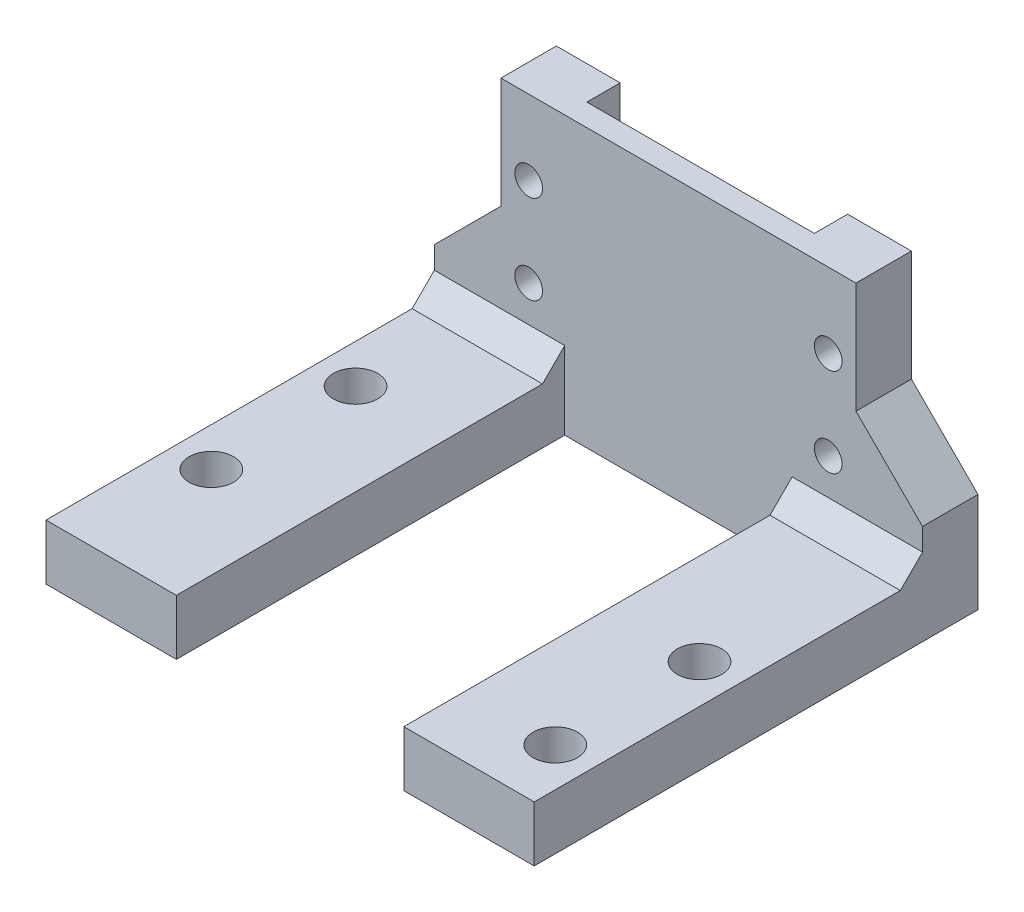
SolidWorks part; units mm, degrees
ref_plane "Płaszczyzna przednia" through (0, 0, 0) normal (0, 0, 1) x (1, 0, 0)
ref_plane "Płaszczyzna górna" through (0, 0, 0) normal (0, 1, 0) x (1, 0, 0)
ref_plane "Płaszczyzna prawa" through (0, 0, 0) normal (1, 0, 0) x (0, 0, -1)
sketch "Szkic1" plane through (0, 0, 0) normal (0, 0, 1) x (1, 0, 0)
  line L1 (16, -12.5) -> (-16, -12.5)
  line L2 (16, -12.5) -> (16, 12.5)
  line L3 (16, 12.5) -> (-16, 12.5)
  line L4 (-16, -12.5) -> (-16, 12.5)
  line L5 (16, -12.5) -> (-16, 12.5) construction
  line L6 (16, 12.5) -> (-16, -12.5) construction
  point P0 (0, 0)
  dimension "D1" = 32
  dimension "D2" = 25
extrude "Dodanie-wyciągnięcie1" add sketch "Szkic1" along normal blind 2
sketch "Szkic2" plane through (0, 0, 0) normal (0, 0, -1) x (-1, 0, 0)
  line L0 (-16, 12.5) -> (16, 12.5) construction
  line L1 (-10.25, 12.5) -> (10.25, 12.5)
  line L2 (-10.25, 12.5) -> (-10.25, -12.5)
  line L3 (-10.25, -12.5) -> (10.25, -12.5)
  line L4 (10.25, 12.5) -> (10.25, -12.5)
  line L5 (16, -12.5) -> (-16, -12.5) construction
  line L6 (0, 0) -> (0, 12.5) construction
  line L7 (16, 12.5) -> (16, -12.5) construction
  line L8 (-16, 12.5) -> (16, 12.5)
  line L9 (-16, 12.5) -> (-16, -12.5)
  line L10 (-16, -12.5) -> (16, -12.5)
  line L11 (16, 12.5) -> (16, -12.5)
  line M6 (16, -12.5) -> (16, 12.5)
  line M7 (16, 12.5) -> (-16, 12.5)
  line M8 (-16, 12.5) -> (-16, -12.5)
  line M9 (-16, -12.5) -> (16, -12.5)
  dimension "D1" = 20.5
extrude "Dodanie-wyciągnięcie2" add sketch "Szkic2" along normal blind 3 contours L2 M7 M8 M9 | L4 M7 M9 M6
sketch "Szkic4" plane through (0, 0, -3) normal (0, 0, -1) x (-1, 0, 0)
  line L0 (0, 0) -> (0, -12.5) construction
  line L1 (10.25, -12.5) -> (-10.25, -12.5) construction
  line L2 (-16, -12.5) -> (-10.25, -12.5) construction
  line L3 (-22, -7.5) -> (22, -7.5)
  line L4 (-22, -7.5) -> (-22, -12.5)
  line L5 (-22, -12.5) -> (22, -12.5)
  line L6 (22, -7.5) -> (22, -12.5)
  line L7 (-22, -7.5) -> (22, -12.5) construction
  line L8 (-22, -12.5) -> (22, -7.5) construction
  line L10 (-22, -7.5) -> (-10.25, -7.5)
  line L11 (-22, -7.5) -> (-22, -12.5)
  line L12 (-22, -12.5) -> (-10.25, -12.5)
  line L13 (-10.25, -7.5) -> (-10.25, -12.5)
  line L14 (22, -7.5) -> (10.25, -7.5)
  line L15 (22, -7.5) -> (22, -12.5)
  line L16 (22, -12.5) -> (10.25, -12.5)
  line L17 (10.25, -7.5) -> (10.25, -12.5)
  point P4 (0, -10)
  line M6 (10.25, 12.5) -> (10.25, -12.5)
  line M7 (10.25, -12.5) -> (16, -12.5)
  line M8 (16, -12.5) -> (16, 12.5)
  dimension "D1" = 5
  dimension "D2" = 44
extrude "Dodanie-wyciągnięcie3" add sketch "Szkic4" against normal blind 40 contours L13 L3 L4 L5 | L6 L3 L5 M8 | L3 M6 M7 M8
sketch "Szkic5" plane through (0, 0, 2) normal (0, 0, 1) x (1, 0, 0)
  line L0 (-13.5, 5.75) -> (-13.5, -2.25) construction
  line L1 (0, 0) -> (0, 12.5) construction
  line L8 (-10.25, -7.5) -> (-10.25, -12.5)
  line L9 (-10.25, -12.5) -> (10.25, -12.5)
  line L10 (10.25, -12.5) -> (10.25, -7.5)
  line L11 (10.25, -7.5) -> (16, -7.5)
  line L12 (16, -7.5) -> (16, 12.5)
  line L13 (16, 12.5) -> (-16, 12.5)
  line L14 (-16, 12.5) -> (-16, -7.5)
  line L15 (-16, -7.5) -> (-10.25, -7.5)
  line L19 (10.25, -7.5) -> (16, -7.5)
  circle A1 centre (-13.5, 5.75) radius 1.25
  circle A3 centre (-13.5, -2.25) radius 1.25
  circle A4 centre (13.5, -2.25) radius 1.25
  circle A5 centre (13.5, 5.75) radius 1.25
  dimension "D4" = 5.75
  dimension "D5" = 2.5
  dimension "D2" = 8
  dimension "D3" = 13.5
  dimension "D1" = 0
extrude "Wytnij-wyciągnięcie1" cut sketch "Szkic5" against normal blind 35 contours A1 | A3 | A4 | A5
sketch "Szkic7" plane through (0, -7.5, 0) normal (0, 1, 0) x (1, 0, 0)
  line L0 (-18.5, -12.6) -> (-18.5, -25.6) construction
  line L1 (-22, -37) -> (-12, -37) construction
  line L2 (-22, -37) -> (-22, 3) construction
  line L3 (-10.25, -37) -> (-22, -37) construction
  line L4 (-17, -37) -> (-17, 3) construction
  line L5 (-16, 3) -> (-22, 3) construction
  line L6 (0, 0) -> (0, -30.5329) construction
  line L7 (18.5, -18.6) -> (18.5, -31.6) construction
  circle A8 centre (18.5, -31.6) radius 2
  circle A9 centre (18.5, -18.6) radius 2
  circle A10 centre (-18.5, -25.6) radius 2
  circle A11 centre (-18.5, -12.6) radius 2
  dimension "D2" = 13
  dimension "D3" = 13
  dimension "D4" = 12.6
  dimension "D5" = 18.6
  dimension "D1" = 10
  dimension "D6" = 18.5
  dimension "D7" = 18.5
extrude "Wytnij-wyciągnięcie2" cut sketch "Szkic7" against normal blind 35
chamfer "Sfazowanie1" distance 10 angle 45 4 edges at (19, -7.5, -3) (16, -7.5, -0.5) (-16, -7.5, -0.5) (-19, -7.5, -3)
chamfer "Sfazowanie2" distance 2 angle 45 1 edges at (16.125, -7.5, 2)
